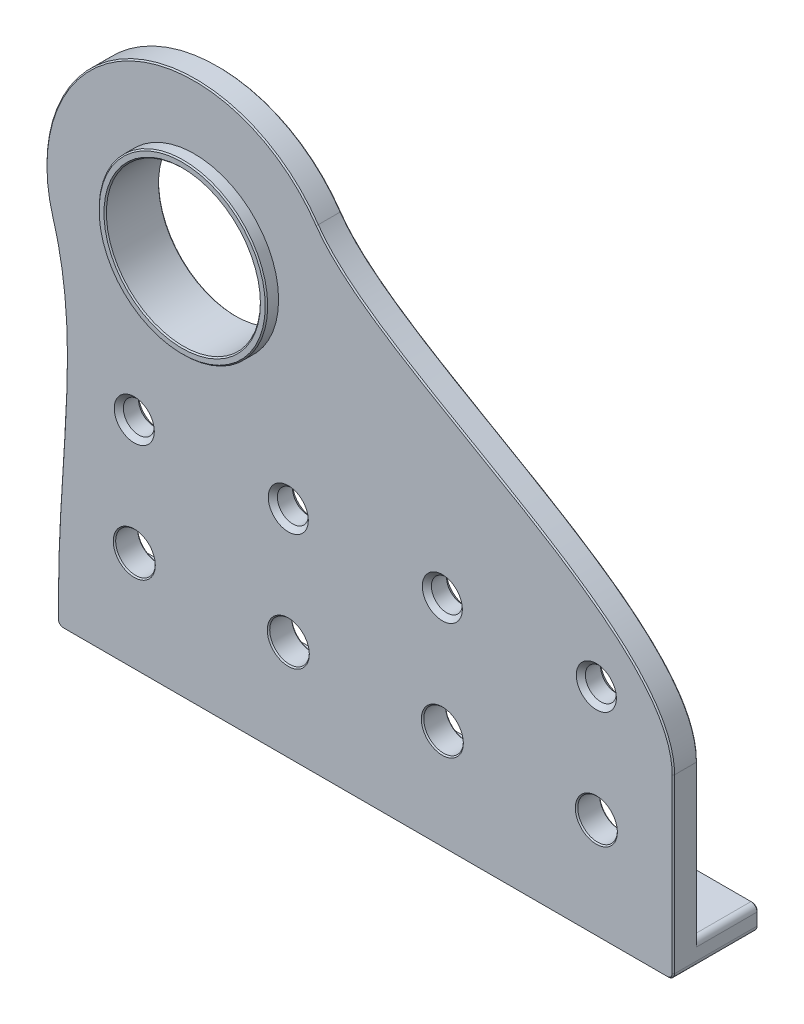
SolidWorks part; units mm, degrees
ref_plane "Front Plane" through (0, 0, 0) normal (0, 0, 1) x (1, 0, 0)
ref_plane "Top Plane" through (0, 0, 0) normal (0, 1, 0) x (1, 0, 0)
ref_plane "Right Plane" through (0, 0, 0) normal (1, 0, 0) x (0, 0, -1)
sketch "main_features_sketch" plane through (0, 0, 0) normal (0, 0, 1) x (1, 0, 0)
  line L0 (-32.6, -60.8) -> (69, -60.8)
  line L1 (-32.6, -48.1) -> (69, -48.1) construction
  line L2 (-32.6, -45.936) -> (-32.6, -50.264) construction
  line L3 (-32.6, -60.8) -> (221.4, -60.8) construction
  line L4 (-32.6, -64.8) -> (69, -64.8)
  line L5 (69, -64.8) -> (69, -60.8)
  line L6 (-32.6, -64.8) -> (-32.6, -60.8)
  line L7 (69, -60.8) -> (69, -35.4)
  line L8 (-1.002, 30.3098) -> (21.8632, -3.2585) construction
  line L9 (69, -11.5867) -> (69, -43.0984) construction
  line L10 (-37.4694, 6.46) -> (-29.2715, -21.1904) construction
  line L11 (-32.6, -35.6082) -> (-32.6, -69.3304) construction
  line L12 (56.3, -64.8) -> (56.3, -60.8)
  line L13 (69, -35.4) -> (-32.6, -35.4) construction
  line L14 (37.25, -64.8) -> (37.25, -60.8)
  circle A0 centre (-10, 0) radius 24.5
  circle A1 centre (-10, 0) radius 15.75
  circle A2 centre (-10, 0) radius 12.7
  circle A3 centre (-10, 0) radius 13.9
  circle A4 centre (-19.9, -48.1) radius 3.2639
  circle A5 centre (5.5, -48.1) radius 3.2639
  circle A6 centre (30.9, -48.1) radius 3.2639
  circle A7 centre (-10, 0) radius 5 construction
  circle A8 centre (56.3, -48.1) radius 3.2639
  spline S0 degree 3 poles (69, -35.4) (69, -15.7052) (20.5779, -1.3714) (10.2488, 13.7926) knots 0 0 0 0 1 1 1 1
  spline S1 degree 3 poles (-32.6, -60.8) (-32.6, -39.7236) (-28.7387, -22.9874) (-33.4893, -6.9643) knots 0 0 0 0 1 1 1 1
  dimension "D1" = 25.4
  dimension "D2" = 31.5
  dimension "D3" = 49
  dimension "D4" = 27.8
  dimension "D5" = 6.5278
  dimension "D6" = 4
  dimension "D7" = 25.4
  dimension "D8" = 25.4
  dimension "D9" = 25.4
  dimension "D10" = 25.4
  dimension "D11" = 12.7
  dimension "D12" = 12.7
  dimension "D14" = 12.7
  dimension "D16" = 19.05
extrude "outer_ring" add sketch "main_features_sketch" along normal blind 4 contours A0 A1 | A1 A2 | A3 A2 region at (-20.207, 21.5079, 0) region at (-25.3045, 0, 0) region at (-23.5068, 0, 0)
ref_axis "center_axis" through (-10, 0, 4) along (0, 0, -1)
ref_plane "center_plane" through (-10, 0, 0) normal (1, 0, 0) x (0, 0, -1)
extrude "inner_ring" add sketch "main_features_sketch<3>" against normal blind 3 contours A3 A2 | A1 A3 region at (-25.3045, 0, 0) region at (-23.5068, 0, 0)
sketch "main_features_sketch<3>" plane through (0, 0, 0) normal (0, 0, 1) x (1, 0, 0) same geometry as "main_features_sketch"
extrude "support_ring" add sketch "main_features_sketch<4>" along normal blind 6 contours A3 A2 region at (-23.5068, 0, 0)
sketch "main_features_sketch<4>" plane through (0, 0, 0) normal (0, 0, 1) x (1, 0, 0) same geometry as "main_features_sketch"
sketch "groove_sketch" plane through (-10, 0, 0) normal (1, 0, 0) x (0, 0, -1)
  line L0 (2.35, 15.75) -> (1.65, 15.05)
  line L1 (3, 15.75) -> (0, 15.75) construction
  line L2 (1.65, 15.05) -> (0.95, 15.75)
  line L3 (0.95, 15.75) -> (2.35, 15.75)
  dimension "D1" = 0.7
  dimension "D2" = 1.35
revolve "groove" cut sketch "groove_sketch" angle 360 about axis through (-10, 0, 4) along (0, 0, -1)
extrude "plate" add sketch "main_features_sketch<5>" along normal up to surface (4 mm away) contours S1 L0 L7 S0 A0 A8 A6 A5 A4 | L6 L4 L5 L0 | L4 L0 | L4 L0 L6 | L14 L4 L12 L0 | L12 L4 L5 L0 region at (19.8589, -35.9075, 0) region at (2.325, -62.8, 0) region at (46.775, -62.8, 0) region at (62.65, -62.8, 0) up to face at (3.9, 0, 4)
sketch "main_features_sketch<5>" plane through (0, 0, 0) normal (0, 0, 1) x (1, 0, 0) same geometry as "main_features_sketch"
extrude "ledge" add sketch "main_features_sketch<6>" against normal blind 10 contours L12 L4 L5 L0 | L4 L14 L0 L6 region at (2.325, -62.8, 0) region at (62.65, -62.8, 0)
sketch "main_features_sketch<6>" plane through (0, 0, 0) normal (0, 0, 1) x (1, 0, 0) same geometry as "main_features_sketch"
hole_wizard "1/4-20 Tapped Hole1" positions "Sketch1" profile "Sketch2" tap size "1/4-20" standard "ANSI Inch" end condition through all
sketch "Sketch1" plane through (0, 0, 4) normal (0, 0, 1) x (1, 0, 0)
  line L2 (69, -35.4) -> (-31.4314, -35.4) construction
  line L4 (-19.9, -29.05) -> (56.3, -29.05) construction
  line L6 (-19.9, -29.05) -> (-19.9, -48.1) construction
  circle A0 centre (-19.9, -48.1) radius 3.2639 construction
  spline S0 degree 3 poles (-32.6, -60.8) (-32.6, -39.7236) (-28.7387, -22.9874) (-33.4893, -6.9643) knots 0 0 0 0 1 1 1 1 construction
  point P0 (56.3, -29.05)
  point P33 (30.9, -29.05)
  point P37 (-19.9, -29.05)
  point P44 (5.5, -29.05)
  dimension "D1" = 6.35
  dimension "D2" = 25.4
  dimension "D3" = 25.4
  dimension "D4" = 25.4
sketch "Sketch2" plane through (56.3, -29.05, 4) normal (1, 0, 0) x (0, -1, 0)
  line L0 (0, 0) -> (0, 4)
  line L1 (0, 4) -> (3.302, 4)
  line L2 (2.5527, 3.2507) -> (2.5527, 0.7493)
  line L3 (2.5527, 0.7493) -> (3.302, 0)
  line L5 (3.302, 0) -> (0, 0)
  line L6 (-2.5527, 0.7493) -> (-3.302, 0) construction
  line L7 (3.302, 4) -> (2.5527, 3.2507)
  line L8 (-3.302, 4) -> (-2.5527, 3.2507) construction
  line L11 (0, -6.35) -> (0, 107.95) construction
  dimension "Thru Tap Drill Dia." = 5.1054
  dimension "Thru Tap Drill Depth" = 4
  dimension "Near C'Sink Dia." = 6.604
  dimension "Near C'Sink Angle" = 90
  dimension "Far C'Sink Dia." = 6.604
  dimension "Far C'Sink Angle" = 90
cosmetic thread "Hole Thread7" parameters "D2"=6.35
cosmetic thread "Hole Thread11" parameters "D2"=6.35
cosmetic thread "Hole Thread12" parameters "D2"=6.35
cosmetic thread "Hole Thread13" parameters "D2"=6.35
fillet "Fillet1" radius 1 8 edges at (69, -64.8, -3) (69, -60.8, -5) (56.3, -64.8, -5) (56.3, -60.8, -5) (37.25, -60.8, -5) (37.25, -64.8, -5) (-32.6, -64.8, -3) (-32.6, -60.8, -5)
chamfer "Chamfer1" distance 0.2 angle 45 42 edges at (3.9, 0, 6) (2.7, 0, 6) (5.75, 0, -3) (2.7, 0, -3) (-16.6361, -48.1, 4) (-16.6361, -48.1, 0) (8.7639, -48.1, 4) (8.7639, -48.1, 0) (34.1639, -48.1, 4) (34.1639, -48.1, 0) (59.5639, -48.1, 4) (59.5639, -48.1, 0) (68.7071, -61.0929, -10) (62.65, -60.8, -10) (56.5929, -61.0929, -10) (56.3, -62.8, -10) (56.5929, -64.5071, -10) (62.65, -64.8, -10) (68.7071, -64.5071, -10) (69, -62.8, -10) (-32.3071, -61.0929, -10) (-32.6, -62.8, -10) (-32.3071, -64.5071, -10) (2.325, -64.8, -10) (36.9571, -64.5071, -10) (37.25, -62.8, -10) (36.9571, -61.0929, -10) (2.325, -60.8, -10) (68.7071, -64.5071, 4) (18.2, -64.8, 4) (69, -49.6, 4) (-32.3071, -64.5071, 4) (-32.6, -62.3, 4) (-20.5041, 22.134, 4) (46.775, -64.8, 0) (69, -48.6, 0) (-32.6, -61.3, 0) (-20.5041, 22.134, 0)
